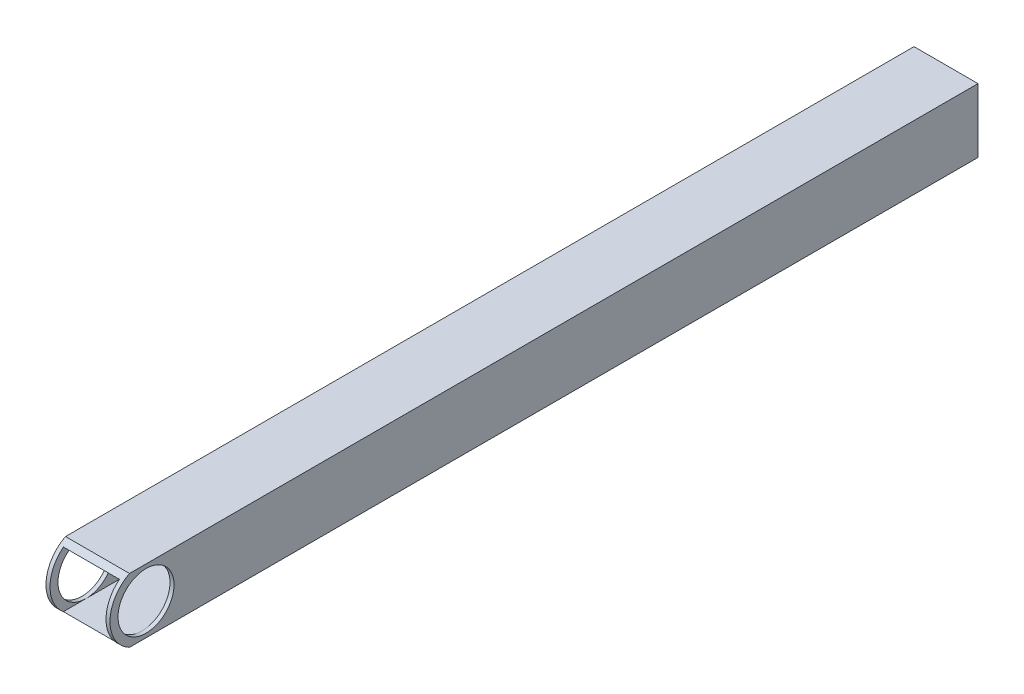
SolidWorks part; units mm, degrees
material "6061 Alloy"
ref_plane "Front Plane" through (0, 0, 0) normal (0, 0, 1) x (1, 0, 0)
ref_plane "Top Plane" through (0, 0, 0) normal (0, 1, 0) x (1, 0, 0)
ref_plane "Right Plane" through (0, 0, 0) normal (1, 0, 0) x (0, 0, -1)
sketch "Sketch1" plane through (0, 0, 0) normal (0, 0, 1) x (1, 0, 0)
  line L1 (12.7, -12.7) -> (-12.7, -12.7)
  line L2 (12.7, -12.7) -> (12.7, 12.7)
  line L3 (12.7, 12.7) -> (-12.7, 12.7)
  line L4 (-12.7, -12.7) -> (-12.7, 12.7)
  line L5 (12.7, -12.7) -> (-12.7, 12.7) construction
  line L6 (12.7, 12.7) -> (-12.7, -12.7) construction
  point P0 (0, 0)
  dimension "D1" = 25.4
extrude "Extrude-Thin1" add sketch "Sketch1" along normal mid plane 349.25 thin thin type one direction reverse wall 1.5875
sketch "Sketch2" plane through (12.7, 0, 0) normal (1, 0, 0) x (0, 0, -1)
  line L0 (-174.625, -12.7) -> (-174.625, 12.7) construction
  line L1 (-174.625, -12.7) -> (174.625, -12.7) construction
  circle A0 centre (-155.575, 0) radius 11.1125
  dimension "D1" = 22.225
  dimension "D2" = 19.05
  dimension "D3" = 12.7
extrude "Cut-Extrude1" cut sketch "Sketch2" against normal through all
sketch "Sketch3" plane through (12.7, 0, 0) normal (1, 0, 0) x (0, 0, -1)
  line L0 (-155.575, 14.2875) -> (-174.625, 14.2875)
  line L3 (-174.625, 14.2875) -> (-174.625, -12.7)
  line L4 (-174.625, -12.7) -> (-162.1204, -12.7)
  arc A0 (-155.575, 14.2875) -> (-162.1204, -12.7) centre (-155.575, 0) ccw
  circle A1 centre (-155.575, 0) radius 11.1125 construction
  dimension "D1" = 3.175
extrude "Cut-Extrude2" cut sketch "Sketch3" against normal through all
